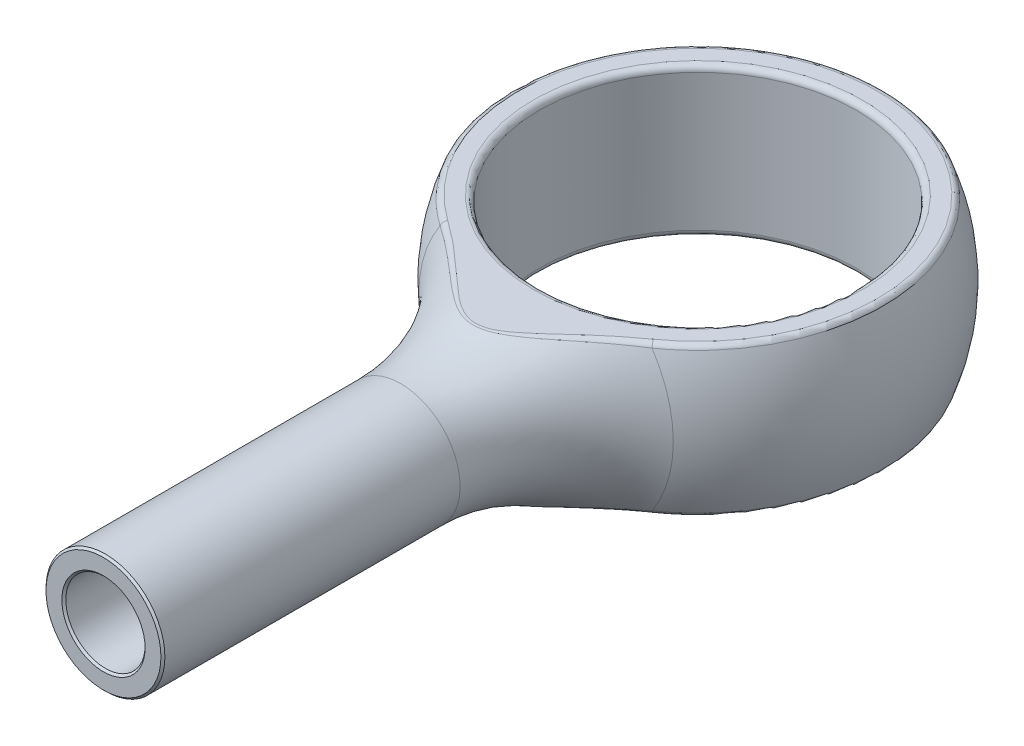
SolidWorks part; units mm, degrees
ref_plane "Front Plane" through (0, 0, 0) normal (0, 0, 1) x (1, 0, 0)
ref_plane "Top Plane" through (0, 0, 0) normal (0, 1, 0) x (1, 0, 0)
ref_plane "Right Plane" through (0, 0, 0) normal (1, 0, 0) x (0, 0, -1)
sketch "Sketch1" plane through (0, 0, 0) normal (0, 1, 0) x (1, 0, 0)
  line L0 (-1.5, -15) -> (1.5, -15)
  line L1 (1.5, -15) -> (1.5, -7.5)
  line L2 (-1.5, -15) -> (-1.5, -7.5)
  circle A0 centre (0, 0) radius 5
  circle A1 centre (0, 0) radius 4
  circle A2 centre (0, 0) radius 2 construction
  arc A3 (-1.5, -7.5) -> (-3.2117, -3.8321) centre (-6.2857, -7.5) ccw
  arc A4 (1.5, -7.5) -> (3.2117, -3.8321) centre (6.2857, -7.5) cw
  point P8 (0, -15)
  dimension "D1" = 10
  dimension "D2" = 8
  dimension "D3" = 4
  dimension "D4" = 15
  dimension "D5" = 3
  dimension "D6" = 7.5
sketch "Sketch2" plane through (0, 0, 0) normal (0, 1, 0) x (1, 0, 0)
  line L0 (-1.5, -15) -> (1.5, -15) construction
  line L1 (-1.5, -15) -> (-1.5, -7.5) construction
  line L2 (-1.5, -15) -> (0, -15)
  line L3 (-1.5, -15) -> (-1.5, -7.5)
  line L4 (0, 5) -> (0, -15)
  circle A0 centre (0, 0) radius 5 construction
  arc A1 (-1.5, -7.5) -> (-3.2117, -3.8321) centre (-6.2857, -7.5) ccw construction
  arc A2 (0, 5) -> (-3.2117, -3.8321) centre (0, 0) ccw
  arc A3 (-1.5, -7.5) -> (-3.2117, -3.8321) centre (-6.2857, -7.5) ccw
revolve "Revolve1" add sketch "Sketch2" angle 360 about L4
sketch "Sketch3" plane through (0, 0, 0) normal (1, 0, 0) x (0, 0, -1)
  line L0 (-6.9143, 1.875) -> (13.7492, 1.875)
  line L1 (13.7492, 1.875) -> (13.7492, 11.3821)
  line L2 (13.7492, 11.3821) -> (-22.0683, 11.3821)
  line L3 (-22.0683, 11.3821) -> (-9.7821, 2.7792)
  line L4 (0, 0) -> (17.0964, 0) construction
  line L5 (13.7492, -11.3821) -> (-22.0683, -11.3821)
  line L6 (13.7492, -1.875) -> (13.7492, -11.3821)
  line L7 (-6.9143, -1.875) -> (13.7492, -1.875)
  line L8 (-22.0683, -11.3821) -> (-9.7821, -2.7792)
  arc A0 (-6.9143, 1.875) -> (-9.7821, 2.7792) centre (-6.9143, 6.875) cw
  arc A1 (-6.9143, -1.875) -> (-9.7821, -2.7792) centre (-6.9143, -6.875) ccw
  dimension "D1" = 5
  dimension "D2" = 145
  dimension "D3" = 3.75
extrude "Cut-Extrude1" cut sketch "Sketch3" against normal blind 10 and the other way blind 10
sketch "Sketch4" plane through (0, 0, 0) normal (0, 1, 0) x (1, 0, 0)
  circle A0 centre (0, 0) radius 4 construction
  circle A1 centre (0, 0) radius 4
extrude "Cut-Extrude2" cut sketch "Sketch4" against normal blind 10 and the other way blind 10
fillet "Fillet1" radius 0.15 6 edges at (-0.1405, -1.875, 5.6305) (0, 1.875, -4.6351) (0, 1.875, 4) (0, -1.875, -4) (0, -1.875, -4.6351) (0.1405, 1.875, 5.6305)
sketch "Sketch5" plane through (0, 0, 15) normal (0, 0, 1) x (1, 0, 0)
  circle A0 centre (0, 0) radius 1
  dimension "D1" = 2
extrude "Cut-Extrude3" cut sketch "Sketch5" against normal blind 5
chamfer "Chamfer1" distance 0.05 angle 45 2 edges at (-1.5, 0, 15) (1, 0, 15)
